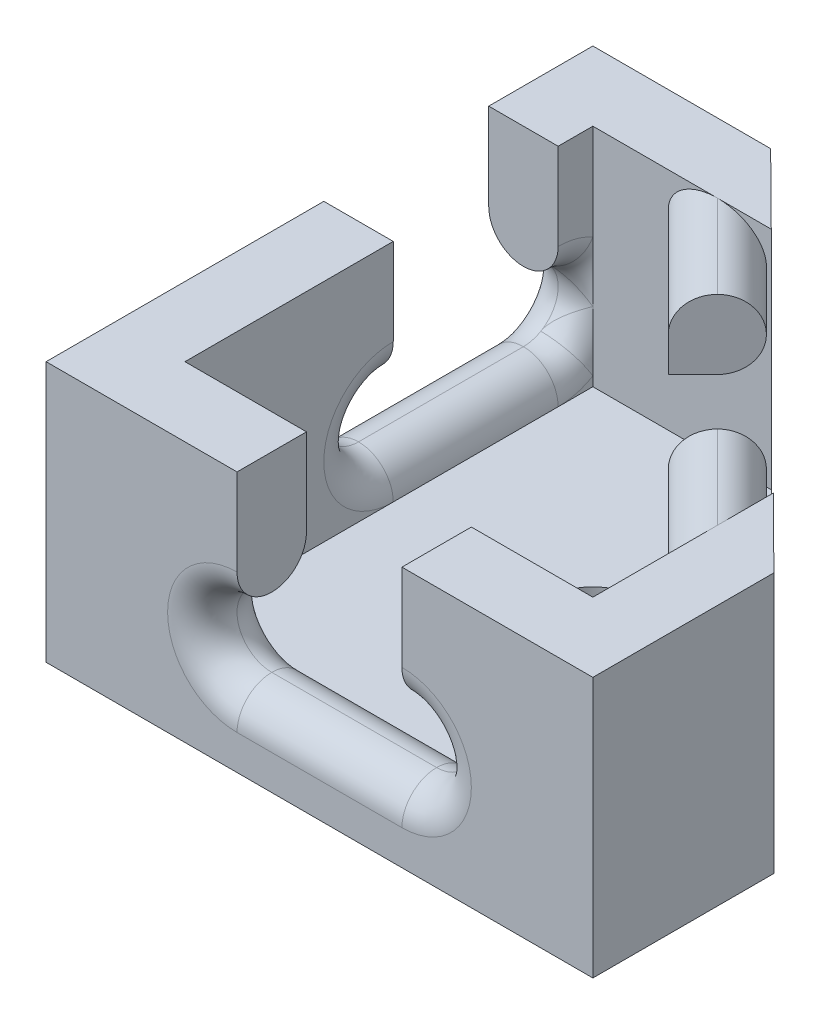
SolidWorks part; units mm, degrees
ref_plane "Front Plane" through (0, 0, 0) normal (0, 0, 1) x (1, 0, 0)
ref_plane "Top Plane" through (0, 0, 0) normal (0, 1, 0) x (1, 0, 0)
ref_plane "Right Plane" through (0, 0, 0) normal (1, 0, 0) x (0, 0, -1)
sketch "Sketch1" plane through (0, 0, 0) normal (0, 1, 0) x (1, 0, 0)
  line L0 (0, 15.75) -> (15.75, 0) construction
  line L1 (0, 0) -> (15.75, 0)
  line L2 (0, 0) -> (0, 15.75)
  line L3 (0, 15.75) -> (15.75, 15.75)
  line L4 (15.75, 0) -> (15.75, 15.75)
  circle A0 centre (7.875, 7.875) radius 1.25
  dimension "D2" = 2.5
  dimension "D1" = 15.75
extrude "BaseBoss-Extrude1" add sketch "Sketch1" along normal blind 1
sketch "Sketch2" plane through (0, 1, 0) normal (0, 1, 0) x (1, 0, 0)
  line L0 (0, 15.75) -> (0, 0) construction
  line L1 (0, 15.75) -> (15.75, 15.75)
  line L2 (0, 15.75) -> (0, 0)
  line L3 (0, 0) -> (15.75, 0)
  line L4 (15.75, 15.75) -> (15.75, 0)
  line L6 (2, 13.75) -> (13.75, 13.75)
  line L7 (2, 13.75) -> (2, 2)
  line L8 (2, 2) -> (13.75, 2)
  line L9 (13.75, 13.75) -> (13.75, 2)
  dimension "D1" = 2
  dimension "D2" = 2
  dimension "D3" = 2
  dimension "D4" = 2
extrude "WallsBoss-Extrude2" add sketch "Sketch2" along normal blind 4.5
sketch "AngleSketch3" plane through (0, 5.5, 0) normal (0, 1, 0) x (1, 0, 0)
  line L0 (7, 13.75) -> (13.75, 7)
  line L1 (13.75, 13.75) -> (2, 13.75) construction
  line L2 (13.75, 2) -> (13.75, 13.75) construction
  line L3 (13.75, 2) -> (13.75, 13.75) construction
  line L4 (4.1716, 13.75) -> (13.75, 4.1716)
  line L5 (13.75, 13.75) -> (2, 13.75) construction
  line L6 (0, 15.75) -> (0, 0) construction
  line L7 (0, 15.75) -> (15.75, 15.75)
  line L8 (0, 15.75) -> (0, 0)
  line L9 (0, 0) -> (15.75, 0)
  line L10 (15.75, 15.75) -> (15.75, 0)
  line L11 (15.75, 15.75) -> (0, 15.75) construction
  line L12 (4.1716, 13.75) -> (2, 13.75)
  line L13 (2, 13.75) -> (2, 2)
  line L14 (2, 2) -> (13.75, 2)
  line L15 (13.75, 2) -> (13.75, 4.1716)
  line L16 (7, 13.75) -> (13.75, 13.75)
  line L17 (13.75, 13.75) -> (13.75, 7)
  dimension "D3" = 2
  dimension "D1" = 9.5459
  dimension "D2" = 45
extrude "AngleBoss-Extrude3" add sketch "AngleSketch3" along normal blind 2
sketch "Sketch4" plane through (0, 0, 0) normal (-1, 0, 0) x (0, 0, 1)
  line L0 (-12.75, 3) -> (-8, 3) construction
  line L1 (-12.75, 4) -> (-8, 4)
  line L2 (-12.75, 2) -> (-8, 2)
  line L3 (-15.75, 0) -> (0, 0) construction
  line L4 (-15.75, 7.5) -> (-15.75, 0) construction
  arc A0 (-12.75, 4) -> (-12.75, 2) centre (-12.75, 3) ccw
  arc A1 (-8, 2) -> (-8, 4) centre (-8, 3) ccw
  point P2 (-10.375, 3)
  dimension "D1" = 2
  dimension "D2" = 2
  dimension "D3" = 3
  dimension "D4" = 4.75
extrude "InCut-Extrude1" cut sketch "Sketch4" against normal blind 2
sketch "Sketch5" plane through (0, 0, 0) normal (0, 0, 1) x (1, 0, 0)
  line L0 (5.5, 3) -> (10.25, 3) construction
  line L1 (5.5, 4) -> (10.25, 4)
  line L2 (5.5, 2) -> (10.25, 2)
  line L3 (0, 7.5) -> (0, 0) construction
  line L4 (0, 0) -> (15.75, 0) construction
  arc A0 (5.5, 4) -> (5.5, 2) centre (5.5, 3) ccw
  arc A1 (10.25, 2) -> (10.25, 4) centre (10.25, 3) ccw
  point P2 (7.875, 3)
  dimension "D1" = 2
  dimension "D4" = 2
  dimension "D2" = 4.75
  dimension "D3" = 5.5
extrude "OutCut-Extrude2" cut sketch "Sketch5" against normal blind 2
sketch "Sketch7" plane through (0, 7.5, 0) normal (0, 1, 0) x (1, 0, 0)
  line L0 (5.121, 15.75) -> (15.75, 5.215)
  line L1 (15.75, 15.75) -> (0, 15.75) construction
  line L2 (15.75, 0) -> (15.75, 15.75) construction
  line L3 (15.75, 5.215) -> (15.75, 15.75)
  line L4 (15.75, 15.75) -> (5.121, 15.75)
extrude "Cut-Extrude2" cut sketch "Sketch7" against normal through all
fillet "InFillet1" radius 1 4 edges at (0, 3, -13.75) (0, 4, -10.375) (0, 3, -7) (0, 2, -10.375)
fillet "OutFillet2" radius 1 4 edges at (11.25, 3, 0) (7.875, 2, 0) (4.5, 3, 0) (7.875, 4, 0)
fillet "InFillet3" radius 1 5 edges at (2, 2.2929, -13.4571) (2, 3.7071, -13.4571) (2, 4, -10.375) (2, 3, -7) (2, 2, -10.375)
fillet "OutFillet4" radius 1 4 edges at (11.25, 3, -2) (7.875, 2, -2) (4.5, 3, -2) (7.875, 4, -2)
sketch "Sketch6" plane through (0, 7.5, 0) normal (0, 1, 0) x (1, 0, 0)
  line L0 (0, 15.75) -> (0, 0) construction
  line L1 (0, 12.75) -> (2, 12.75)
  line L2 (0, 12.75) -> (0, 8)
  line L3 (0, 8) -> (2, 8)
  line L4 (2, 12.75) -> (2, 8)
  line L5 (2, 2) -> (13.75, 2) construction
  line L6 (5.5, 2) -> (10.25, 2)
  line L7 (5.5, 2) -> (5.5, 0)
  line L8 (5.5, 0) -> (10.25, 0)
  line L9 (10.25, 2) -> (10.25, 0)
  line L10 (0, 0) -> (15.75, 0) construction
  line L11 (2, 13.75) -> (2, 2) construction
  line L12 (5.121, 15.75) -> (0, 15.75) construction
  line L13 (7.2814, 10.6402) -> (10.6402, 7.2814)
  line L14 (13.75, 4.1716) -> (4.1716, 13.75) construction
  line L15 (10.6402, 7.2814) -> (12.0544, 8.6956)
  line L16 (7, 13.75) -> (13.75, 7) construction
  line L17 (12.0544, 8.6956) -> (8.6956, 12.0544)
  line L18 (8.6956, 12.0544) -> (7.2814, 10.6402)
  dimension "D3" = 3
  dimension "D1" = 4.75
  dimension "D2" = 5.5
  dimension "D4" = 2.398
extrude "Cut-Extrude1" cut sketch "Sketch6" against normal blind 4
fillet "Fillet5" radius 1 2 edges at (12.9022, 7.5, -7.8478) (7.8478, 7.5, -12.9022)
fillet "Fillet6" radius 1 2 edges at (12.1951, 7.5, -5.7265) (5.7265, 7.5, -12.1951)
fillet "Fillet7" radius 1 2 edges at (12.9022, 5.5, -7.8478) (7.8478, 5.5, -12.9022)
equation "\"D1@Sketch1\"=\"ClampWidth\""
equation "\"RibbonCableWidth\"= 6.75mm"
equation "\"RibbonCableInnerHypotonus\"= sqr ( \"RibbonCableWidth\" ^ 2 * 2 )"
equation "\"M2.5HoleDiameter\"= 2.5mm"
equation "\"FastenerTabHoleCenterFromSide\"= 2mm"
equation "\"ClampWallWidth\"= 2mm"
equation "\"ClampWidth\"= \"RibbonCableWidth\" + \"ClampWallWidth\" * 2 + \"RibbonCableWidthExtension\""
equation "\"ClampHeight\"= \"BaseBoss\" + \"RibbonCableUpperWallHeight\" + \"ClampBridgeHeight\""
equation "\"BaseBoss\"= 1mm"
equation "\"RibbonCableLowerWallHeight\"= 2mm"
equation "\"RibbonCableOuterHypotonus\"= sqr ( ( \"ClampWallWidth\" ^ 2 ) * 2 ) + \"RibbonCableInnerHypotonus\" + sqr ( ( \"ClampWallWidth\" ^ 2 ) * 2 )"
equation "\"RibbonCableHeight\"=2"
equation "\"D1@BaseBoss-Extrude1\" = \"BaseBoss\""
equation "\"D1@Sketch2\"=\"ClampWallWidth\""
equation "\"D2@Sketch2\"=\"ClampWallWidth\""
equation "\"D3@Sketch2\"=\"ClampWallWidth\""
equation "\"D4@Sketch2\"=\"ClampWallWidth\""
equation "\"D1@WallsBoss-Extrude2\"=\"RibbonCableUpperWallHeight\""
equation "\"D1@AngleSketch3\" = \"RibbonCableInnerHypotonus\""
equation "\"RibbonCableWidthExtension\"= 5mm"
equation "\"D3@AngleSketch3\" = \"ClampWallWidth\""
equation "\"D1@AngleBoss-Extrude3\" = \"ClampWallWidth\""
equation "\"D2@Sketch1\"=\"M2.5HoleDiameter\""
equation "\"D1@Sketch4\"=\"RibbonCableHeight\""
equation "\"D2@Sketch4\"=\"RibbonCableLowerWallHeight\""
equation "\"D3@Sketch4\"=\"RibbonCableHeight\"/2 + \"ClampWallWidth\""
equation "\"D4@Sketch4\"=\"RibbonCableWidth\" - \"RibbonCableHeight\""
equation "\"D1@InCut-Extrude1\" = \"ClampWallWidth\""
equation "\"D1@Sketch5\"=\"RibbonCableHeight\""
equation "\"D2@Sketch5\"=\"RibbonCableWidth\"-\"RibbonCableHeight\""
equation "\"D3@Sketch5\"=(\"ClampWidth\" - \"RibbonCableWidth\" + \"RibbonCableHeight\")/2 "
equation "\"D1@OutCut-Extrude2\" = \"ClampWallWidth\""
equation "\"ClampBridgeHeight\"= 2mm"
equation "\"RibbonCableUpperWallHeight\"= \"RibbonCableLowerWallHeight\" + \"RibbonCableHeight\" + .5mm"
equation "\"D1@Sketch6\"=\"RibbonCableWidth\"-2mm"
equation "\"D2@Sketch6\"=(\"ClampWidth\" - \"RibbonCableWidth\" + 2 )/2"
equation "\"D3@Sketch6\"=\"ClampWallWidth\" + \"RibbonCableHeight\"/2"
equation "\"D4@Sketch6\"=(\"RibbonCableInnerHypotonus\" - \"RibbonCableWidth\" + 2 )/2"
equation "\"D1@Cut-Extrude1\"=\"RibbonCableHeight\" + 2mm"
equation "\"D4@Sketch5\"=\"RibbonCableLowerWallHeight\""
